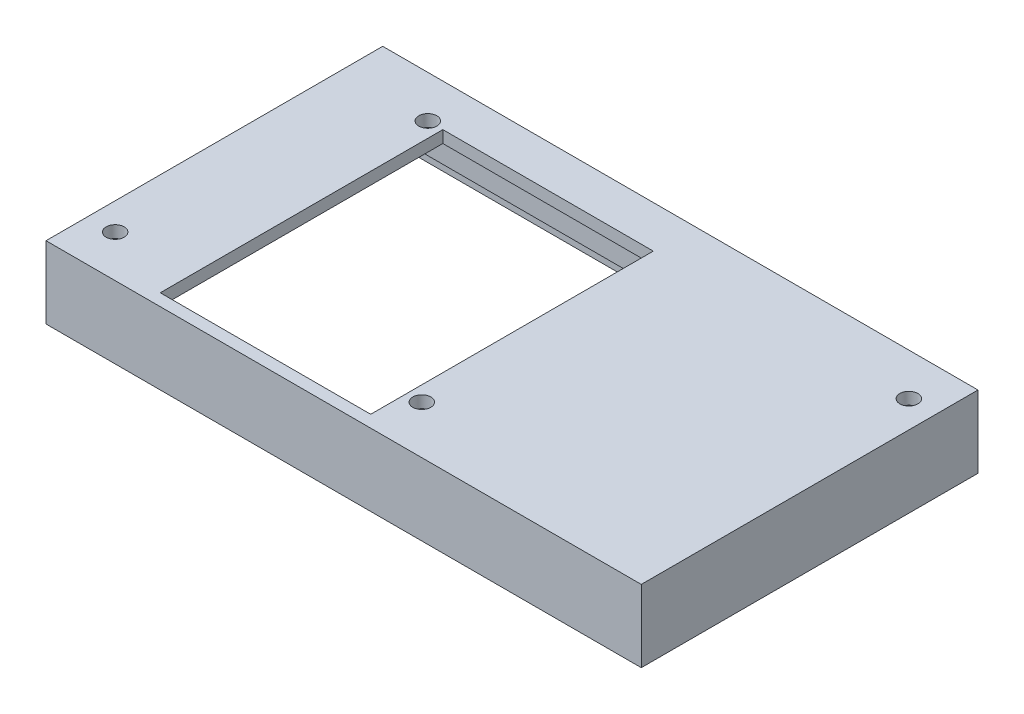
SolidWorks part; units mm, degrees
ref_plane "Front Plane" through (0, 0, 0) normal (0, 0, 1) x (1, 0, 0)
ref_plane "Top Plane" through (0, 0, 0) normal (0, 1, 0) x (1, 0, 0)
ref_plane "Right Plane" through (0, 0, 0) normal (1, 0, 0) x (0, 0, -1)
sketch "Sketch1" plane through (0, 0, 0) normal (0, 1, 0) x (1, 0, 0)
  line L0 (-35, 21) -> (5, -20) construction
  line L1 (-47.5, 26) -> (47.5, 26)
  line L2 (-47.5, 26) -> (-47.5, -26)
  line L3 (-47.5, -26) -> (47.5, -26)
  line L4 (47.5, 26) -> (47.5, -26)
  line L5 (-47.5, 26) -> (47.5, -26) construction
  line L6 (-47.5, -26) -> (47.5, 26) construction
  line L7 (-49.5, 28) -> (49.5, 28)
  line L8 (-49.5, 28) -> (-49.5, -28)
  line L9 (-49.5, -28) -> (49.5, -28)
  line L10 (49.5, 28) -> (49.5, -28)
  line L11 (-49.5, 28) -> (49.5, -28) construction
  line L12 (-49.5, -28) -> (49.5, 28) construction
  line L17 (-32.5, 21) -> (2.5, 21)
  line L18 (-32.5, 21) -> (-32.5, -26)
  line L19 (-32.5, -26) -> (2.5, -26)
  line L20 (2.5, 21) -> (2.5, -26)
  line L21 (-32.5, 21) -> (2.5, -26) construction
  line L22 (-32.5, -26) -> (2.5, 21) construction
  line L23 (-48.5, 27) -> (48.5, 27)
  line L24 (-48.5, 27) -> (-48.5, -27)
  line L25 (-48.5, -27) -> (48.5, -27)
  line L26 (48.5, 27) -> (48.5, -27)
  line L27 (-48.5, 27) -> (48.5, -27) construction
  line L28 (-48.5, -27) -> (48.5, 27) construction
  point P0 (0, 0)
  point P6 (0, 0)
  point P11 (-15, -2.5)
  point P16 (5, -20)
  point P17 (-35, 21)
  point P18 (0, 0)
  point P23 (45, 21)
  point P24 (-45, -21)
  point P25 (0, 0)
  point P29 (-15, 0.5)
  dimension "D1" = 95
  dimension "D2" = 52
  dimension "D3" = 2
  dimension "D4" = 2
  dimension "D5" = 45
  dimension "D6" = 35
  dimension "D7" = 47
  dimension "D8" = 6
  dimension "D10" = 40
  dimension "D11" = 41
  dimension "D12" = 1
  dimension "D13" = 1
  dimension "D14" = 5
  dimension "D15" = 2.5
  dimension "D16" = 5
  dimension "D17" = 2.5
extrude "Boss-Extrude1" add sketch "Sketch1" along normal blind 2 contours L17 L20 L3 L4 L1 L2 L18 | L26 L23 L24 L25 L1 L4 L3 L2 | L10 L7 L8 L9 L23 L26 L25 L24 region at (7.4886, 0, -1.2481) region at (0, 0, -27.8863) region at (0, 0, -26.889)
extrude "Boss-Extrude2" add sketch "Sketch1<3>" against normal blind 10 contours L10 L7 L8 L9 L23 L26 L25 L24 region at (0, 0, -27.8863)
sketch "Sketch1<3>" plane through (0, 0, 0) normal (0, 1, 0) x (1, 0, 0) same geometry as "Sketch1"
extrude "Boss-Extrude3" add sketch "Sketch1<4>" against normal blind 8 contours L26 L23 L24 L25 L1 L4 L3 L2 region at (0, 0, -26.889)
sketch "Sketch1<4>" plane through (0, 0, 0) normal (0, 1, 0) x (1, 0, 0) same geometry as "Sketch1"
hole_wizard "Ø3.0 (3) Diameter Hole1" positions "Sketch5" profile "Sketch6" hole size "Ø3.0" standard "ANSI Metric" end condition through all
sketch "Sketch5" plane through (0, 0, 0) normal (0, -1, 0) x (-1, 0, 0)
  point P0 (-45, 21)
  point P3 (45, -21)
  point P6 (35, 21)
  point P9 (-5, -20)
sketch "Sketch6" plane through (45, 0, -21) normal (1, 0, 0) x (0, 0, -1)
  line L0 (0, 0) -> (0, 2)
  line L1 (0, 2) -> (1.5, 2)
  line L2 (1.5, 2) -> (1.5, 0)
  line L5 (1.5, 0) -> (0, 0)
  line L11 (0, -6.35) -> (0, 107.95) construction
  dimension "Thru Hole Dia." = 3
  dimension "Thru Hole Depth" = 2
sketch "Sketch7" plane through (-49.5, 0, 0) normal (-1, 0, 0) x (0, 0, 1)
  line L0 (-28, -10) -> (28, -10) construction
  line L1 (8, -10) -> (-12, -10)
  line L2 (8, -10) -> (8, -5)
  line L3 (8, -5) -> (-12, -5)
  line L4 (-12, -10) -> (-12, -5)
  line L5 (28, 2) -> (28, -10) construction
  line L6 (-28, 0) -> (28, 0) construction
  dimension "D1" = 20
  dimension "D2" = 20
  dimension "D3" = 5
extrude "Cut-Extrude1" cut sketch "Sketch7" against normal up to surface (2 mm away) up to face at (-47.5, -4, 0)
sketch "Sketch8" plane through (0, 0, -28) normal (0, 0, -1) x (-1, 0, 0)
  line L0 (49.5, -10) -> (-49.5, -10) construction
  line L1 (-29.5, -10) -> (-19.5, -10)
  line L2 (-29.5, -10) -> (-29.5, -5)
  line L3 (-29.5, -5) -> (-19.5, -5)
  line L4 (-19.5, -10) -> (-19.5, -5)
  line L5 (49.5, 0) -> (-49.5, 0) construction
  line L6 (-49.5, 2) -> (-49.5, -10) construction
  dimension "D1" = 5
  dimension "D2" = 10
  dimension "D3" = 20
extrude "Cut-Extrude2" cut sketch "Sketch8" against normal up to next contours L2 L3 L4 L1
